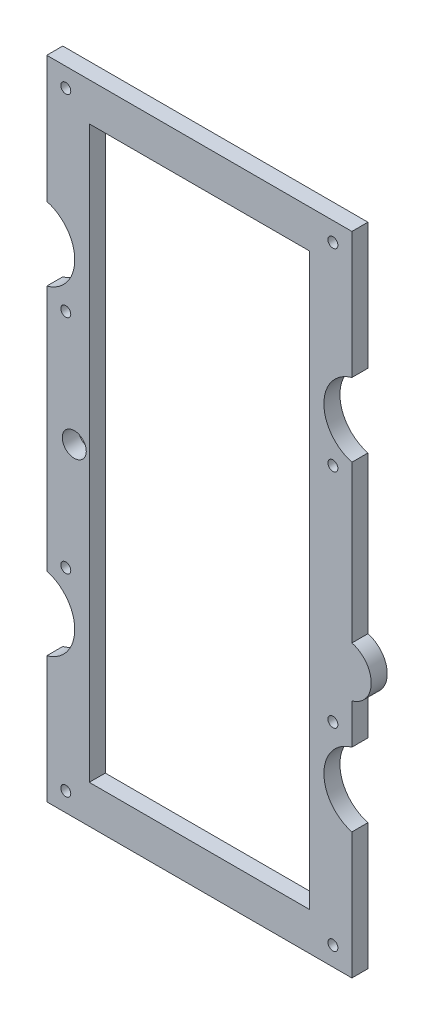
SolidWorks part; units mm, degrees
material "ABS"
ref_plane "Front Plane" through (0, 0, 0) normal (0, 0, 1) x (1, 0, 0)
ref_plane "Top Plane" through (0, 0, 0) normal (0, 1, 0) x (1, 0, 0)
ref_plane "Right Plane" through (0, 0, 0) normal (1, 0, 0) x (0, 0, -1)
sketch "Sketch1" plane through (0, 0, 0) normal (0, 0, 1) x (1, 0, 0)
  line L172 (-61.0801, -938.3303) -> (-61.0801, -1061.6697)
  line L173 (-61.0801, -1098.3303) -> (-61.0801, -1161.5626)
  line L174 (-61.0801, -1161.5626) -> (91.4199, -1161.5626)
  line L175 (91.4199, -1161.5626) -> (91.4199, -1098.3303)
  line L176 (91.4199, -1061.6697) -> (91.4199, -1041.5969)
  line L177 (91.4199, -1016.5631) -> (91.4199, -938.3303)
  line L178 (91.4199, -901.6697) -> (91.4199, -838.4374)
  line L179 (91.4199, -838.4374) -> (-61.0801, -838.4374)
  line L180 (-61.0801, -838.4374) -> (-61.0801, -901.6697)
  arc A81 (-61.0801, -938.3303) -> (-61.0801, -901.6697) centre (-66.0801, -920) ccw
  arc A82 (-61.0801, -1098.3303) -> (-61.0801, -1061.6697) centre (-66.0801, -1080) ccw
  arc A83 (91.4199, -1061.6697) -> (91.4199, -1098.3303) centre (96.4199, -1080) ccw
  arc A84 (91.4199, -1041.5969) -> (91.4199, -1016.5631) centre (88.1478, -1029.08) ccw
  arc A85 (91.4199, -901.6697) -> (91.4199, -938.3303) centre (96.4199, -920) ccw
  circle A131 centre (-51.5801, -847.9374) radius 2.5
  circle A137 centre (81.9199, -847.9374) radius 2.5
  circle A140 centre (81.9199, -944.5357) radius 2.5
  circle A143 centre (-51.5801, -944.5357) radius 2.5
  circle A146 centre (-51.5801, -1055.4643) radius 2.5
  circle A149 centre (81.9199, -1055.4643) radius 2.5
  circle A152 centre (81.9199, -1152.0626) radius 2.5
  circle A155 centre (-51.5801, -1152.0626) radius 2.5
extrude "Boss-Extrude1" add sketch "Sketch1" along normal blind 8
ref_plane "Plane1" through (0, 0, 4) normal (0, 0, 1) x (1, 0, 0)
sketch "Sketch3" plane through (0, 0, 8) normal (0, 0, 1) x (1, 0, 0)
  line L0 (91.4199, -977.4467) -> (-116.7456, -977.4467)
  line L1 (91.4199, -1016.5631) -> (91.4199, -938.3303) construction
  line L2 (-116.7456, -977.4467) -> (-212.7029, -785.3719)
  line L3 (-212.7029, -785.3719) -> (106.6532, -745.8336)
  line L4 (106.6532, -745.8336) -> (149.6809, -765.6027)
  line L5 (193.1812, -822.6125) -> (91.4199, -977.4467)
  line L6 (193.1812, -822.6125) -> (149.6809, -765.6027)
extrude "Cut-Extrude2" [suppressed] cut sketch "Sketch3" against normal through all
sketch "Sketch4" [suppressed] plane through (0, -977.4467, 0) normal (0, 1, 0) x (1, 0, 0)
  line L0 (-61.0801, -8) -> (-61.0801, 0) construction
  line L1 (-61.0801, -2) -> (-49.0801, -2)
  line L2 (-61.0801, -2) -> (-61.0801, -6)
  line L3 (-61.0801, -6) -> (-49.0801, -6)
  line L4 (-49.0801, -2) -> (-49.0801, -6)
  line L5 (91.4199, 0) -> (91.4199, -8) construction
  line L6 (91.4199, -2) -> (79.4199, -2)
  line L7 (91.4199, -2) -> (91.4199, -6)
  line L8 (91.4199, -6) -> (79.4199, -6)
  line L9 (79.4199, -2) -> (79.4199, -6)
  line L10 (67.4199, -8) -> (91.4199, -8) construction
  line L11 (-61.0801, 0) -> (-37.0801, 0) construction
  dimension "D1" = 12
  dimension "D2" = 4
  dimension "D3" = 2
  dimension "D4" = 4
  dimension "D5" = 2
  dimension "D6" = 12
extrude "Cut-Extrude3" [suppressed] cut sketch "Sketch4" against normal blind 10
sketch "Sketch5" plane through (0, 0, 0) normal (0, 0, -1) x (-1, 0, 0)
  line L0 (-91.4199, -1161.5626) -> (-91.4199, -1098.3303) construction
  line L1 (-70.1699, -857.5) -> (39.8301, -857.5)
  line L2 (-70.1699, -857.5) -> (-70.1699, -1142.5)
  line L3 (-70.1699, -1142.5) -> (39.8301, -1142.5)
  line L4 (39.8301, -857.5) -> (39.8301, -1142.5)
  line L5 (61.0801, -1161.5626) -> (-91.4199, -1161.5626) construction
  dimension "D1" = 285
  dimension "D2" = 110
  dimension "D3" = 21.25
  dimension "D4" = 19.0626
extrude "Cut-Extrude4" cut sketch "Sketch5" against normal through all
sketch "Sketch6" plane through (0, 0, 8) normal (0, 0, 1) x (1, 0, 0)
  line L0 (-39.8301, -1142.5) -> (-39.8301, -857.5) construction
  circle A0 centre (-47.3301, -1000) radius 6
  dimension "D1" = 12
  dimension "D2" = 7.5
extrude "Cut-Extrude5" cut sketch "Sketch6" against normal through all
